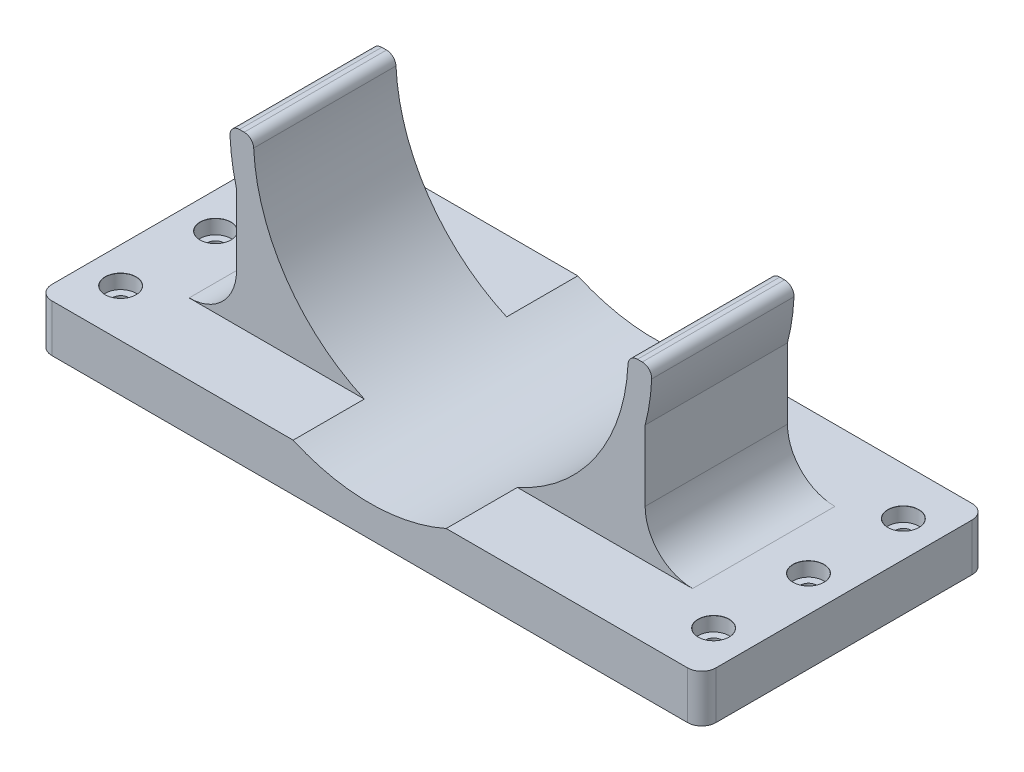
SolidWorks part; units mm, degrees
ref_plane "Front Plane" through (0, 0, 0) normal (0, 0, 1) x (1, 0, 0)
ref_plane "Top Plane" through (0, 0, 0) normal (0, 1, 0) x (1, 0, 0)
ref_plane "Right Plane" through (0, 0, 0) normal (1, 0, 0) x (0, 0, -1)
other "Center of Mass"
sketch "Sketch1" plane through (0, 0, 0) normal (0, 0, 1) x (1, 0, 0)
  line L2 (-70, -36.0562) -> (-16.1308, -36.0562)
  line L3 (-70, -36.0562) -> (-70, -46.0562)
  line L4 (-70, -46.0562) -> (70, -46.0562)
  line L5 (70, -36.0562) -> (70, -46.0562)
  line L6 (39.5, 0) -> (44.5, 0)
  line L7 (-70, -41.0562) -> (70, -41.0562) construction
  line L8 (16.1308, -36.0562) -> (70, -36.0562)
  line L9 (-43.0654, -36.0562) -> (-43.0654, -11.2081)
  line L10 (43.0654, -36.0562) -> (43.0654, -11.2081)
  line L12 (-39.5, 0) -> (-44.5, 0)
  line L13 (0, -39.5) -> (0, -46.0562) construction
  line L14 (-44.2182, 5) -> (44.2182, 5) construction
  line L15 (-39.5, 0) -> (39.5, 0) construction
  arc A0 (-39.5, 0) -> (39.5, 0) centre (0, 0) ccw
  arc A1 (-44.5, 0) -> (-26.0807, -36.0562) centre (0, 0) ccw
  arc A2 (26.0807, -36.0562) -> (44.5, 0) centre (0, 0) ccw
  arc A3 (-44.2182, 5) -> (44.2182, 5) centre (0, 0) ccw construction
  dimension "D1" = 140
  dimension "D2" = 10
  dimension "D3" = 5
extrude "Boss-Extrude3" add sketch "Sketch1" along normal blind 30 and the other way blind 30 contours A0 L2 L3 L4 L5 L8 region at (0, -41.2602, 0)
extrude "Boss-Extrude4" add sketch "Sketch1<6>" along normal blind 15 and the other way blind 15 contours L12 A1 L2 A0 | L8 A2 L6 A0 region at (-34.8305, -19.8543, 0) region at (34.8305, -19.8543, 0)
sketch "Sketch1<6>" plane through (0, 0, 0) normal (0, 0, 1) x (1, 0, 0) same geometry as "Sketch1"
extrude "Boss-Extrude5" add sketch "Sketch1<7>" along normal blind 15 and the other way blind 15 contours A2 L8 L10 | A1 L9 L2 region at (-38.0609, -28.9614, 0) region at (38.0609, -28.9614, 0)
sketch "Sketch1<7>" plane through (0, 0, 0) normal (0, 0, 1) x (1, 0, 0) same geometry as "Sketch1"
fillet "Fillet1" radius 10 2 edges at (43.0654, -36.0562, 0) (-43.0654, -36.0562, 0)
sketch "Sketch2" plane through (0, -36.0562, 0) normal (0, 1, 0) x (1, 0, 0)
  line L0 (62.5, 0) -> (70, 0) construction
  line L1 (-70, 30) -> (70, 30)
  line L2 (-70, 30) -> (-70, -30)
  line L3 (-70, -30) -> (70, -30)
  line L4 (70, 30) -> (70, -30)
  line L5 (-70, 0) -> (-62.5, 0) construction
  line L6 (62.5, 30) -> (62.5, -30) construction
  line L7 (-62.5, 30) -> (-62.5, -30) construction
  point P16 (-62.5, 30)
  point P17 (-62.5, 0)
  point P18 (-62.5, -30)
  dimension "D1" = 7.5
hole_wizard "CBORE for M3 SHCS1" positions "Sketch5" profile "Sketch4" counterbore size "M3" standard "ANSI Metric" end condition through all
sketch "Sketch5" plane through (0, -36.0562, 0) normal (0, 1, 0) x (1, 0, 0)
  point P0 (-62.5, 0)
  point P3 (62.5, 0)
sketch "Sketch4" plane through (-62.5, -36.0562, 0) normal (1, 0, 0) x (0, 0, 1)
  line L0 (0, 0) -> (0, 10)
  line L1 (0, 10) -> (1.7, 10)
  line L3 (1.7, 10) -> (1.7, 3)
  line L4 (3.25, 3) -> (1.7, 3)
  line L5 (3.25, 3) -> (3.25, 0.025)
  line L6 (3.25, 0.025) -> (3.275, 0)
  line L7 (3.275, 0) -> (0, 0)
  line L8 (-3.25, 0.025) -> (-3.275, 0) construction
  line L11 (0, -6.35) -> (0, 107.95) construction
  dimension "Thru Hole Dia." = 3.4
  dimension "Thru Hole Depth" = 10
  dimension "C'Bore Dia." = 6.5
  dimension "C'Bore Depth" = 3
  dimension "Near C'Sink Dia." = 6.55
  dimension "Near C'Sink Angle" = 90
pattern_linear "LPattern1" count 2 spacing 20 along (0, 0, -1) count 2 spacing 20 along (0, 0, 1) of "CBORE for M3 SHCS1" pattern seed only yes
fillet "Fillet2" radius 2 4 edges at (-44.5, 0, 0) (-39.5, 0, 0) (44.5, 0, 0) (39.5, 0, 0)
fillet "Fillet3" radius 3 4 edges at (-70, -41.0562, 30) (-70, -41.0562, -30) (70, -41.0562, -30) (70, -41.0562, 30)
ref_axis "Axis1" through (-43.0654, -26.0562, 15) along (0, 1, 0)
